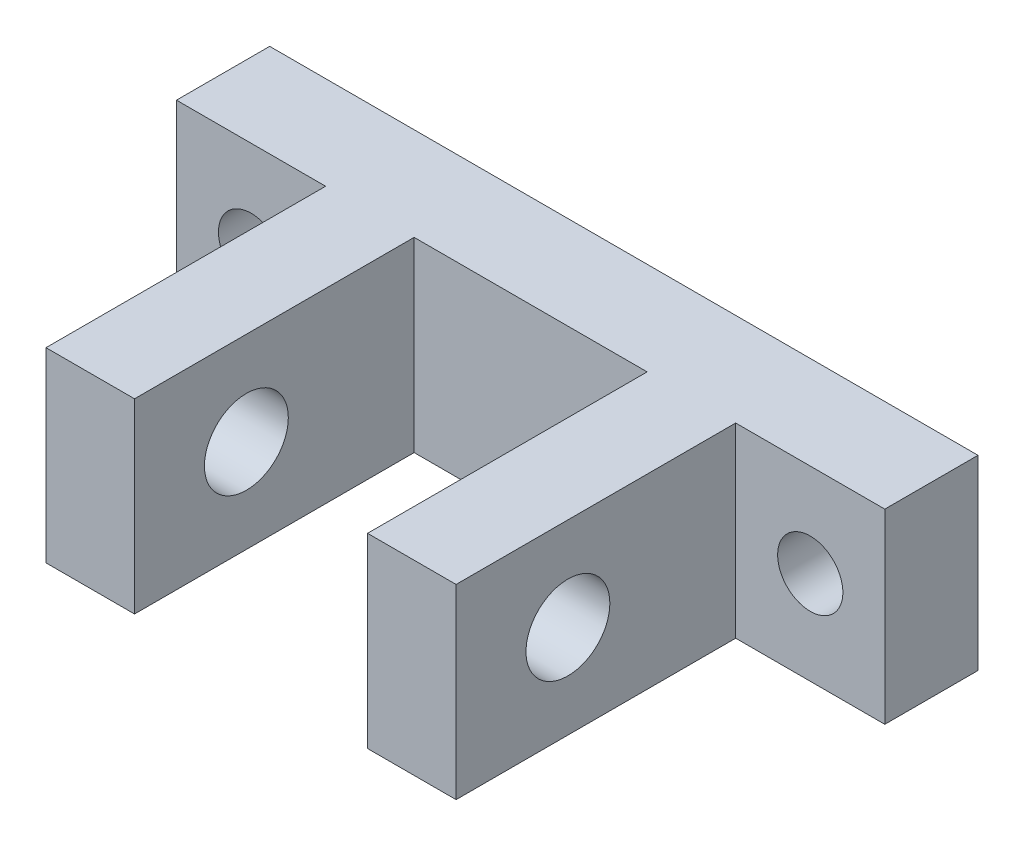
SolidWorks part; units mm, degrees
ref_plane "Front Plane" through (0, 0, 0) normal (0, 0, 1) x (1, 0, 0)
ref_plane "Top Plane" through (0, 0, 0) normal (0, 1, 0) x (1, 0, 0)
ref_plane "Right Plane" through (0, 0, 0) normal (1, 0, 0) x (0, 0, -1)
sketch "Sketch1" plane through (0, 0, 0) normal (0, 1, 0) x (1, 0, 0)
  line L0 (0, 0) -> (0, -20.0709) construction
  line L1 (-11, 0) -> (11, 0)
  line L2 (11, 0) -> (11, -20)
  line L3 (11, -20) -> (6.25, -20)
  line L4 (6.25, -20) -> (6.25, -5)
  line L5 (6.25, -5) -> (-6.25, -5)
  line L6 (-6.25, -20) -> (-6.25, -5)
  line L7 (-11, -20) -> (-6.25, -20)
  line L8 (-11, 0) -> (-11, -20)
  line L9 (6.25, -20) -> (6.25, -5)
  point P9 (0, -5)
  dimension "D1" = 6.25
  dimension "D2" = 4.75
  dimension "D3" = 15
  dimension "D4" = 5
extrude "Boss-Extrude1" add sketch "Sketch1" along normal blind 10 contours L1 L0 L5 L4 L3 L2 | L0 L1 L8 L7 L6 L5 region at (7.2636, 0, 8.1436) region at (-7.2636, 0, 8.1436)
sketch "Sketch2" plane through (11, 0, 0) normal (1, 0, 0) x (0, 0, -1)
  line L0 (-20, 5) -> (0, 5) construction
  line L1 (-20, 10) -> (-20, 0) construction
  line L2 (0, 10) -> (0, 0) construction
  circle A0 centre (-14, 5) radius 2.25
  dimension "D1" = 4.5
  dimension "D2" = 14
extrude "Cut-Extrude1" cut sketch "Sketch2" against normal through all contours A0
sketch "Sketch3" plane through (0, 10, 0) normal (0, 1, 0) x (1, 0, 0)
  line L1 (-19, -5) -> (19, -5)
  line L2 (0, 0) -> (0, -5) construction
  line L3 (-19, 0) -> (19, 0)
  line L4 (19, -5) -> (19, 0)
  line L5 (-11, 0) -> (11, 0) construction
  line L6 (11, 0) -> (11, -20) construction
  line L7 (-19, -5) -> (-19, 0)
  line L8 (6.25, -5) -> (-6.25, -5) construction
  dimension "D1" = 8
extrude "Boss-Extrude2" add sketch "Sketch3" against normal through all
sketch "Sketch4" plane through (0, 0, 5) normal (0, 0, 1) x (1, 0, 0)
  line L0 (-19, 5) -> (-11, 5) construction
  line L1 (-19, 0) -> (-19, 10) construction
  line L2 (-11, 10) -> (-11, 0) construction
  line L3 (-15, 0) -> (-15, 10) construction
  line L6 (0, 0) -> (0, 10) construction
  line L7 (6.25, 0) -> (-6.25, 0) construction
  line L8 (6.25, 10) -> (-6.25, 10) construction
  line L9 (15, 0) -> (15, 10) construction
  line L10 (19, 5) -> (11, 5) construction
  line L11 (-15, 0) -> (-15, 10) construction
  circle A0 centre (-15, 5) radius 1.75
  circle A1 centre (15, 5) radius 1.75
  dimension "D1" = 3.5
  dimension "D2" = 15
extrude "Cut-Extrude2" cut sketch "Sketch4" against normal through all
